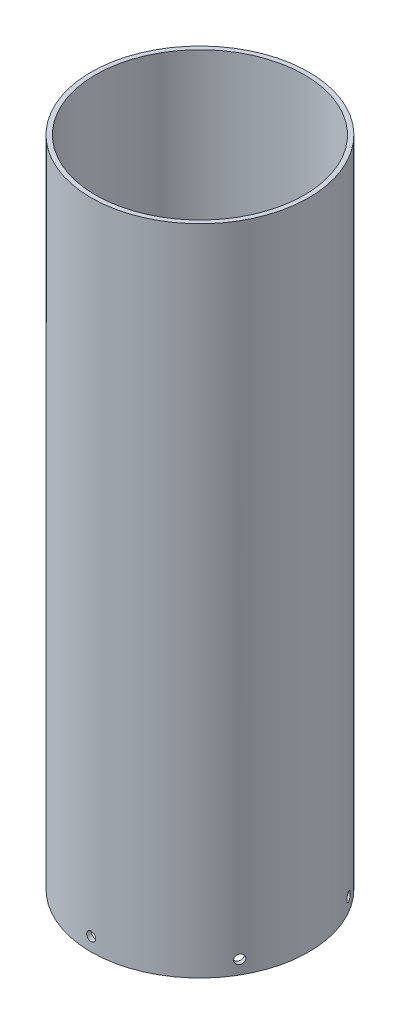
SolidWorks part; units mm, degrees
material "Polycarbonate"
ref_plane "Front Plane" through (0, 0, 0) normal (0, 0, 1) x (1, 0, 0)
ref_plane "Top Plane" through (0, 0, 0) normal (0, 1, 0) x (1, 0, 0)
ref_plane "Right Plane" through (0, 0, 0) normal (1, 0, 0) x (0, 0, -1)
sketch "Sketch2" plane through (0, 0, 0) normal (0, 1, 0) x (1, 0, 0)
  circle A0 centre (0, 0) radius 73.025
  circle A1 centre (0, 0) radius 76.2
  dimension "D1" = 146.05
  dimension "D2" = 152.4
extrude "Boss-Extrude1" add sketch "Sketch2" along normal blind 457.2
sketch "Sketch3" plane through (0, 0, 0) normal (0, 0, 1) x (1, 0, 0)
  line L0 (0, 0) -> (0, 235.745) construction
  line L1 (-76.2, 0) -> (76.2, 0) construction
  circle A0 centre (0, 9.525) radius 3.175
  dimension "D1" = 9.525
extrude "Cut-Extrude1" cut sketch "Sketch3" against normal through all
ref_axis "Axis1" through (0, 0, 0) along (0, 1, 0)
pattern_circular "CirPattern1" count 6 over 360 about axis through (0, 0, 0) along (0, 1, 0) of "Cut-Extrude1"
